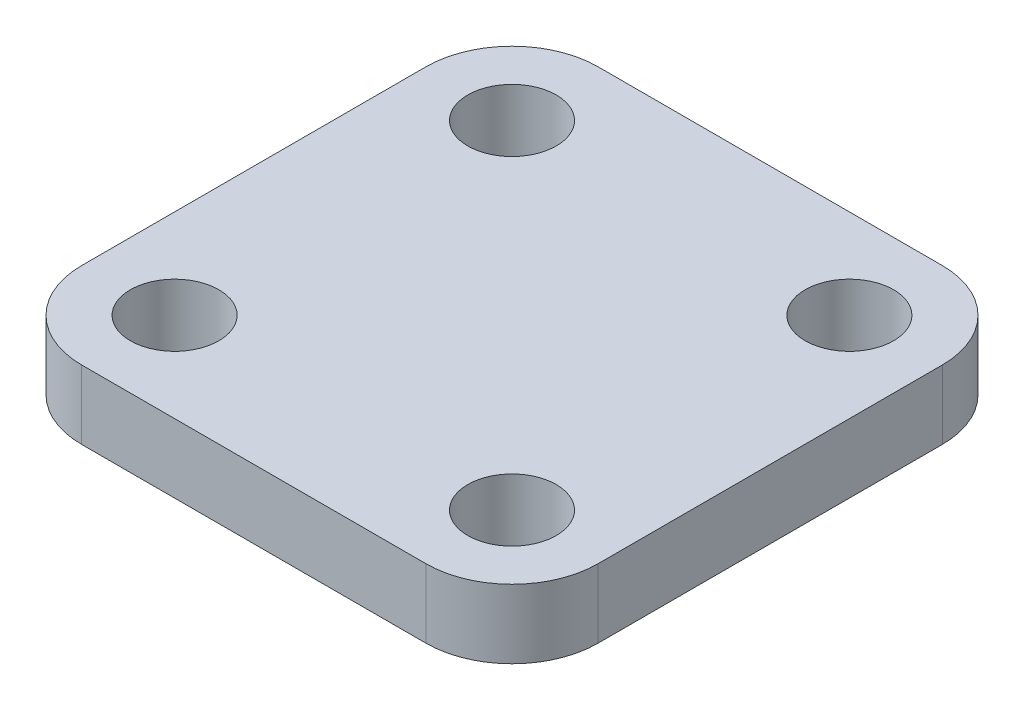
SolidWorks part; units mm, degrees
ref_plane "Front Plane" through (0, 0, 0) normal (0, 0, 1) x (1, 0, 0)
ref_plane "Top Plane" through (0, 0, 0) normal (0, 1, 0) x (1, 0, 0)
ref_plane "Right Plane" through (0, 0, 0) normal (1, 0, 0) x (0, 0, -1)
sketch "Sketch1" plane through (0, 0, 0) normal (0, 1, 0) x (1, 0, 0)
  line L0 (0, 0) -> (9.525, 0) construction
  line L1 (-6.35, 9.525) -> (6.35, 9.525)
  line L2 (-9.525, 6.35) -> (-9.525, -6.35)
  line L3 (-6.35, -9.525) -> (6.35, -9.525)
  line L4 (9.525, 6.35) -> (9.525, -6.35)
  line L5 (-9.525, 9.525) -> (9.525, -9.525) construction
  line L6 (-9.525, -9.525) -> (9.525, 9.525) construction
  line L7 (0, 0) -> (0, 9.525) construction
  circle A1 centre (6.223, 6.223) radius 1.632
  circle A3 centre (6.223, -6.223) radius 1.632
  circle A4 centre (-6.223, -6.223) radius 1.632
  circle A5 centre (-6.223, 6.223) radius 1.632
  arc A6 (-9.525, -6.35) -> (-6.35, -9.525) centre (-6.35, -6.35) ccw
  arc A7 (6.35, -9.525) -> (9.525, -6.35) centre (6.35, -6.35) ccw
  arc A8 (6.35, 9.525) -> (9.525, 6.35) centre (6.35, 6.35) cw
  arc A9 (-6.35, 9.525) -> (-9.525, 6.35) centre (-6.35, 6.35) ccw
  point P0 (0, 0)
  point P29 (0, 0)
  point P30 (5.715, 6.9596)
  dimension "D4" = 3.2639
  dimension "D5" = 3.175
  dimension "D1" = 19.05
  dimension "D2" = 19.05
  dimension "D3" = 3.302
  dimension "D6" = 3.302
extrude "Boss-Extrude1" add sketch "Sketch1" along normal blind 2.54
